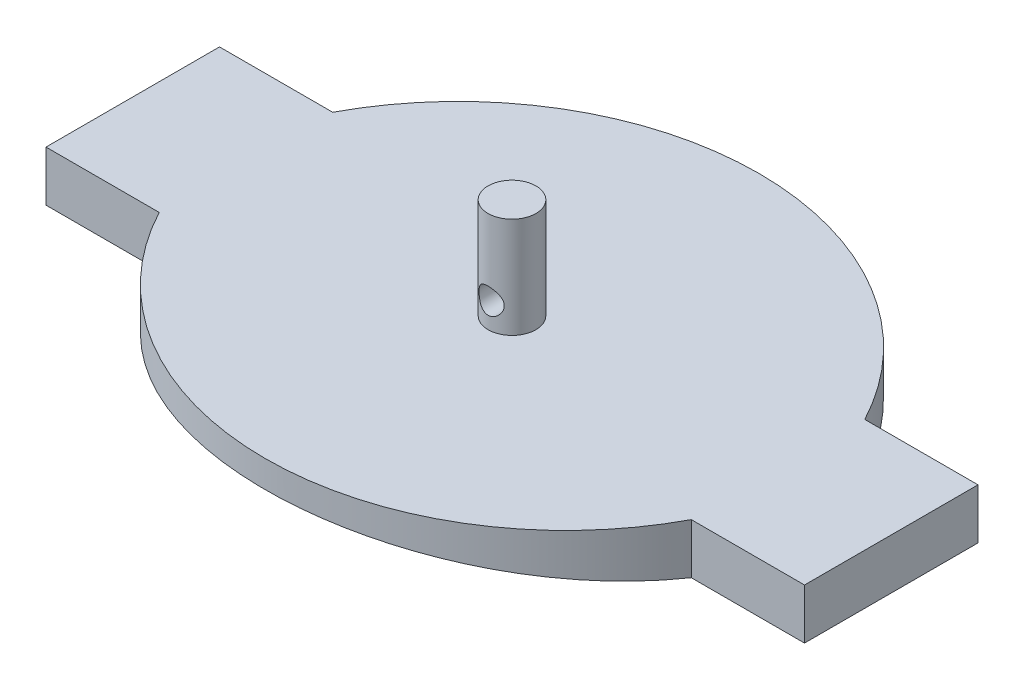
SolidWorks part; units mm, degrees
ref_plane "Front Plane" through (0, 0, 0) normal (0, 0, 1) x (1, 0, 0)
ref_plane "Top Plane" through (0, 0, 0) normal (0, 1, 0) x (1, 0, 0)
ref_plane "Right Plane" through (0, 0, 0) normal (1, 0, 0) x (0, 0, -1)
sketch "Sketch4" plane through (0, 0, 0) normal (0, 1, 0) x (1, 0, 0)
  line L1 (0, -55) -> (0, 55) construction
  line L3 (-52.8407, -44.8867) -> (52.8407, -44.8867) construction
  line L4 (0, 4.1584) -> (0, -93.9317) construction
  line L6 (52.8407, -62.1172) -> (75.3295, -62.1172)
  line L7 (52.8407, -27.6562) -> (75.3295, -27.6562)
  line L8 (75.3295, -62.1172) -> (75.3295, -27.6562)
  line L9 (-52.8407, -27.6562) -> (-75.3295, -27.6562)
  line L10 (-75.3295, -62.1172) -> (-75.3295, -27.6562)
  line L11 (-52.8407, -62.1172) -> (-75.3295, -62.1172)
  arc A1 (-52.8407, -62.1172) -> (52.8407, -62.1172) centre (0, -34.143) ccw
  arc A2 (-52.8407, -27.6562) -> (52.8407, -27.6562) centre (0, -55.6303) cw
  point P16 (0, 0)
extrude "Boss-Extrude3" add sketch "Sketch4" along normal blind 10
sketch "Sketch5" plane through (0, 10, 0) normal (0, 1, 0) x (1, 0, 0)
  line L0 (0, 4.1584) -> (0, -93.9317) construction
  line L1 (-52.8407, -44.8867) -> (52.8407, -44.8867) construction
  line L2 (-52.8407, -27.6562) -> (-52.8407, -62.1172) construction
  line L3 (52.8407, -62.1172) -> (52.8407, -27.6562) construction
  arc A0 (52.8407, -27.6562) -> (-52.8407, -27.6562) centre (0, -55.6303) ccw construction
  arc A1 (-52.8407, -62.1172) -> (52.8407, -62.1172) centre (0, -34.143) ccw construction
  circle A2 centre (0, -44.8867) radius 4.75
  dimension "D1" = 9.5
extrude "Boss-Extrude4" add sketch "Sketch5" along normal blind 20
ref_plane "Plane1" through (0, 0, 40.1367) normal (0, 0, -1) x (-1, 0, 0)
sketch "Sketch6" plane through (0, 0, 40.1367) normal (0, 0, -1) x (-1, 0, 0)
  line L0 (52.8407, 10) -> (-52.8407, 10) construction
  circle A0 centre (0, 15) radius 2.5
  dimension "D1" = 5
  dimension "D2" = 5
extrude "Cut-Extrude1" cut sketch "Sketch6" against normal up to next
ref_plane "Plane2" through (0, 0, 93.9317) normal (0, 0, 1) x (1, 0, 0)
sketch "Sketch7" plane through (0, 0, 93.9317) normal (0, 0, 1) x (1, 0, 0)
  line L0 (-52.8407, 0) -> (52.8407, 0)
  arc A0 (-52.8407, 0) -> (52.8407, 0) centre (0, -298.5918) cw
extrude "Cut-Extrude2" cut sketch "Sketch7" against normal up to next
